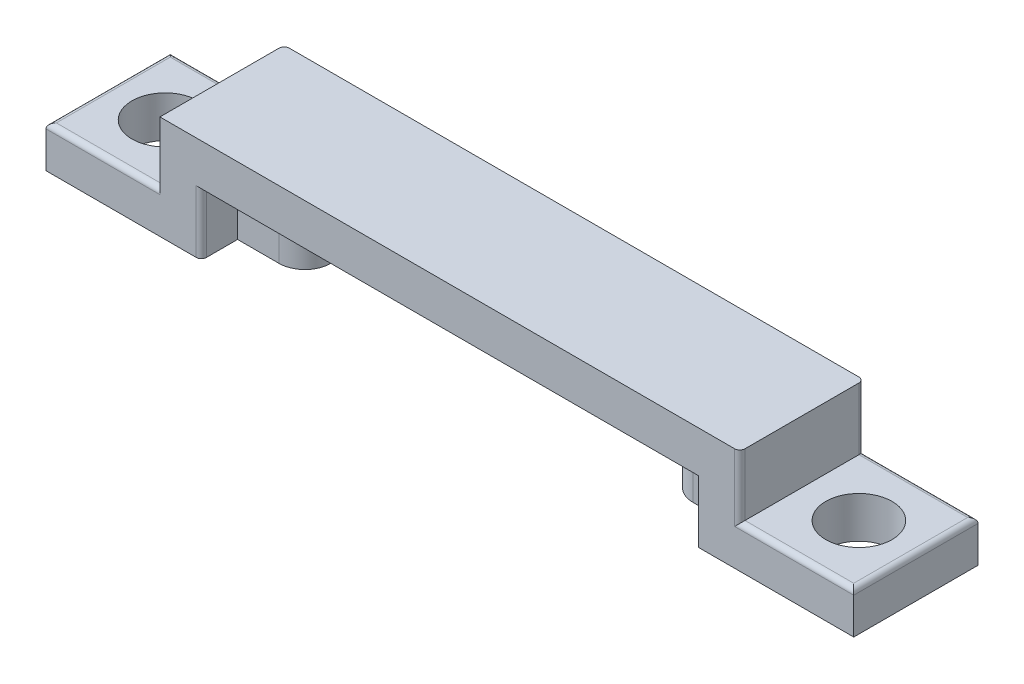
SolidWorks part; units mm, degrees
ref_plane "Ebene vorne" through (0, 0, 0) normal (0, 0, 1) x (1, 0, 0)
ref_plane "Ebene oben" through (0, 0, 0) normal (0, 1, 0) x (1, 0, 0)
ref_plane "Ebene rechts" through (0, 0, 0) normal (1, 0, 0) x (0, 0, -1)
sketch "Skizze1" plane through (0, 0, 0) normal (0, 0, 1) x (1, 0, 0)
  line L0 (0, 0) -> (7.5, 0)
  line L1 (7.5, 0) -> (7.5, 3)
  line L2 (7.5, 3) -> (31.5, 3)
  line L3 (31.5, 3) -> (31.5, 0)
  line L4 (31.5, 0) -> (39, 0)
  line L5 (39, 0) -> (39, 2)
  line L8 (33.5, 5) -> (5.5, 5)
  line L11 (0, 2) -> (0, 0)
  line L12 (33.5, 5) -> (33.5, 2)
  line L13 (-9, 2) -> (48, 2) construction
  line L14 (33.5, 2) -> (39, 2)
  line L15 (5.5, 5) -> (5.5, 2)
  line L16 (-9, 2) -> (48, 2) construction
  line L17 (5.5, 2) -> (0, 2)
  dimension "D1" = 24
  dimension "D2" = 3
  dimension "D3" = 7.5
  dimension "D4" = 7.5
  dimension "D5" = 5
  dimension "D9" = 2
  dimension "D10" = 2
extrude "Aufsatz-Linear austragen1" add sketch "Skizze1" along normal blind 6
sketch "Skizze4" plane through (0, 0, 0) normal (0, -1, 0) x (1, 0, 0)
  line L0 (39, 6) -> (39, 0) construction
  line L1 (31.5, 0) -> (39, 0) construction
  circle A0 centre (36.25, 3) radius 1.6
  dimension "D1" = 3.2
  dimension "D3" = 3
  dimension "D2" = 2.75
extrude "Schnitt-Linear austragen1" cut sketch "Skizze4" against normal blind 3
ref_plane "Ebene1" through (0, 5, 0) normal (0, -1, 0) x (-1, 0, 0)
ref_plane "Ebene2" through (19.5, 0, 0) normal (-1, 0, 0) x (0, 0, 1)
ref_plane "Ebene4" through (0, 0, 3) normal (0, 0, 1) x (1, 0, 0)
sketch "Skizze12" plane through (0, 3, 0) normal (0, -1, 0) x (1, 0, 0)
  line L0 (31.5, 1.75) -> (29.5, 1.75)
  line L1 (31.5, 6) -> (31.5, 0) construction
  line L2 (2.75, 3) -> (-2.75, 3) construction
  line L3 (29.5, 4.25) -> (31.5, 4.25)
  line L4 (31.5, 6) -> (31.5, 0) construction
  line L5 (31.5, 4.25) -> (31.5, 1.75)
  arc A0 (29.5, 1.75) -> (29.5, 4.25) centre (29.5, 3) cw
  dimension "D2" = 1.25
  dimension "D1" = 2
extrude "Aufsatz-Linear austragen2" add sketch "Skizze12" along normal blind 3
mirror "Spiegeln3" about plane through (19.5, 0, 0) normal (-1, 0, 0) of "Aufsatz-Linear austragen2"
mirror "Spiegeln4" about plane through (19.5, 0, 0) normal (-1, 0, 0) of "Schnitt-Linear austragen1"
fillet "Verrundung1" radius 0.25 10 edges at (7.5, 1.5, 6) (33.5, 3.5, 6) (33.5, 3.5, 0) (5.5, 3.5, 0) (2.75, 2, 6) (0, 2, 3) (2.75, 2, 0) (36.25, 2, 0) (39, 2, 3) (36.25, 2, 6)
